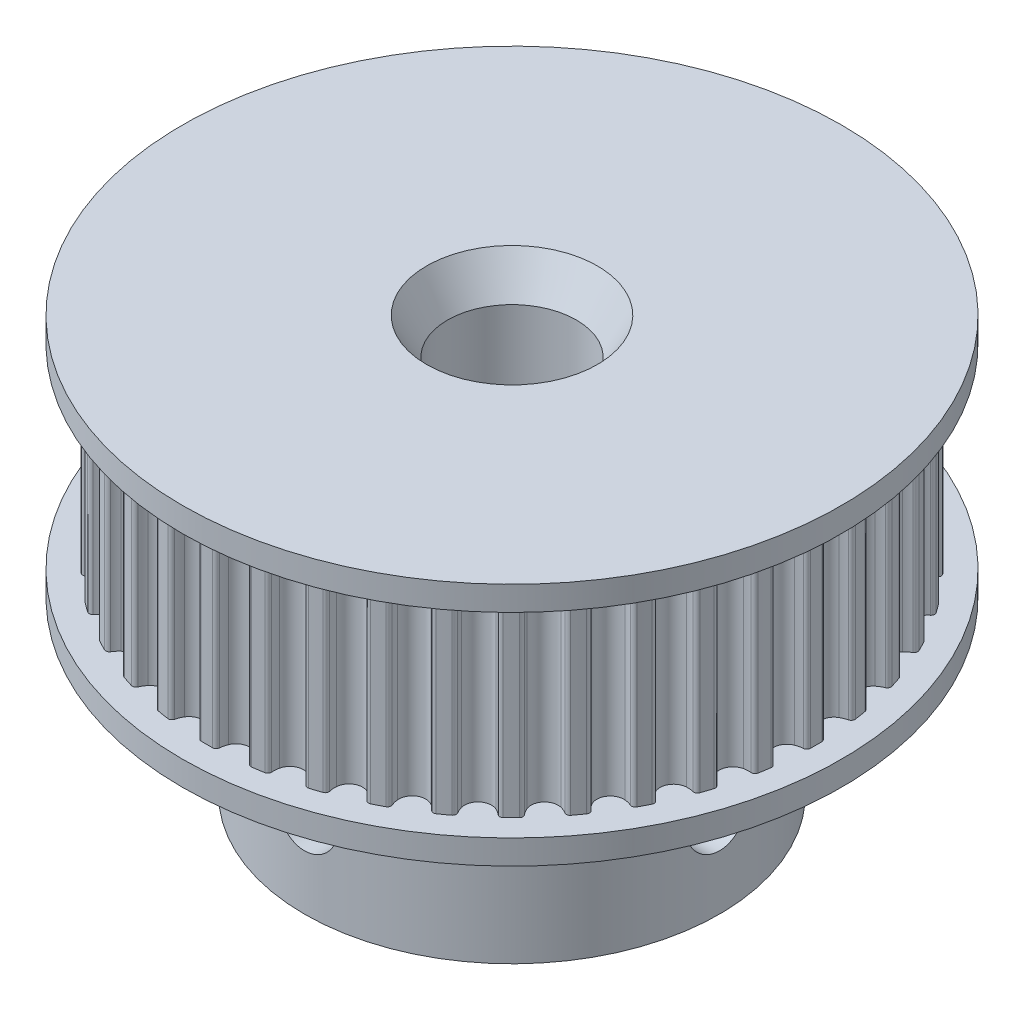
SolidWorks part; units mm, degrees
ref_plane "Front Plane" through (0, 0, 0) normal (0, 0, 1) x (1, 0, 0)
ref_plane "Top Plane" through (0, 0, 0) normal (0, 1, 0) x (1, 0, 0)
ref_plane "Right Plane" through (0, 0, 0) normal (1, 0, 0) x (0, 0, -1)
sketch "Sketch1" plane through (0, 0, 0) normal (0, 1, 0) x (1, 0, 0)
  circle A0 centre (0, 0) radius 13.5
  dimension "D1" = 27
extrude "Boss-Extrude1" add sketch "Sketch1" along normal blind 10
sketch "Sketch6" plane through (0, 0, 0) normal (0, 1, 0) x (1, 0, 0)
  circle A0 centre (0, 0) radius 8.5
  dimension "D2" = 17
extrude "Boss-Extrude2" add sketch "Sketch6" against normal blind 7
sketch "Sketch4" plane through (0, 0, 0) normal (0, 1, 0) x (1, 0, 0)
  circle A1 centre (0, 0) radius 2.64
  dimension "D1" = 5.28
extrude "Cut-Extrude3" cut sketch "Sketch4" along normal through all and the other way through all
ref_plane "Plane1" through (0, 1, 0) normal (0, 1, 0) x (1, 0, 0)
sketch "Sketch2" plane through (0, 1, 0) normal (0, 1, 0) x (1, 0, 0)
  line L0 (0, 0) -> (0, 15.3126) construction
  line L1 (-0.0014, -0.018) -> (0.9816, 12.2246) construction
  line L2 (0, 0) -> (1.407, 12.4893) construction
  line L3 (0, 0) -> (1.1174, 13.9156) construction
  line L4 (0, 12.48) -> (0, 13.8263)
  line L6 (1.9915, 12.3201) -> (2.2063, 13.6491)
  circle A0 centre (0, 0) radius 12.48 construction
  arc A1 (0, 12.48) -> (0.2536, 12.4774) centre (0, 0) cw
  arc A2 (0.2536, 12.4774) -> (0.4002, 12.3379) centre (0.2506, 12.3275) cw
  arc A3 (0.4002, 12.3379) -> (0.4664, 12.0434) centre (1.3978, 12.4077) ccw
  arc A4 (0.4664, 12.0434) -> (1.4613, 11.9635) centre (0.9833, 12.2456) ccw
  circle A5 centre (0, 0) radius 11.73 construction
  circle A6 centre (0, 0) radius 13.11 construction
  arc A7 (1.5737, 12.2437) -> (1.4613, 11.9635) centre (0.6001, 12.4717) cw
  arc A8 (1.7407, 12.358) -> (1.5737, 12.2437) centre (1.7198, 12.2095) ccw
  arc A9 (1.9915, 12.3201) -> (1.7407, 12.358) centre (0, 0) ccw
  arc A10 (0, 13.8263) -> (2.2063, 13.6491) centre (0, 0) cw
  point P16 (0.9989, 12.44)
  point P17 (1.3971, 12.4016)
  point P18 (0.9989, 12.44)
  dimension "D1" = 24.96
  dimension "D2" = 0.15
  dimension "D3" = 1
  dimension "D4" = 0.555
  dimension "D7" = 0.75
  dimension "D8" = 1.38
  dimension "D5" = 0.4
  dimension "D6" = 1
extrude "Cut-Extrude1" cut sketch "Sketch2" along normal blind 8
ref_axis "Axis2" through (0, 10, 0) along (0, -1, 0)
pattern_circular "CirPattern1" count 40 over 360 about axis through (0, 10, 0) along (0, -1, 0) of "Cut-Extrude1"
sketch "Sketch5" plane through (0, 0, 0) normal (0, 0, 1) x (1, 0, 0)
  line L0 (-3.5, 10) -> (0, 10)
  line L1 (13.5, 10) -> (-13.5, 10) construction
  line L5 (-3.5, -7) -> (0, -7)
  line L7 (-3.5, -7) -> (-0.6285, -4.1285)
  line L8 (0, 10) -> (0, 6.1244)
  line L9 (-8.5, -7) -> (8.5, -7) construction
  line L10 (-0.6285, -4.1285) -> (0, -4.1285)
  line L11 (-1.2624, 6.1244) -> (0, 6.1244)
  line L12 (-1.2624, 6.1244) -> (-3.5, 10)
  line L13 (0, -4.1285) -> (0, -7)
  dimension "D1" = 3.5
  dimension "D3" = 3.5
  dimension "D4" = 45
revolve "Cut-Revolve1" cut sketch "Sketch5" angle 360 about axis through (0, 10, 0) along (0, -1, 0)
sketch "Sketch7" plane through (0, 0, 0) normal (0, 0, 1) x (1, 0, 0)
  line L0 (-13.5805, -3.5) -> (12.2971, -3.5) construction
  line L1 (-8.5, 0) -> (8.5, 0) construction
  line L2 (-8.5, -7) -> (8.5, -7) construction
  line L3 (0, 0) -> (0, -10.6921) construction
  circle A0 centre (0, -3.5) radius 1.25
  dimension "D1" = 2.5
extrude "Cut-Extrude4" cut sketch "Sketch7" against normal through all and the other way blind 10
sketch "Sketch8" plane through (0, 0, 0) normal (1, 0, 0) x (0, 0, -1)
  line L0 (-10.2203, -3.5) -> (10.2203, -3.5) construction
  line L1 (-8.5, 0) -> (8.5, 0) construction
  line L2 (-8.5, -7) -> (8.5, -7) construction
  line L3 (0, 0) -> (0, -10.0387) construction
  line L4 (0, 10) -> (0, 0) construction
  circle A0 centre (0, -3.5) radius 1.25
  dimension "D1" = 2.5
extrude "Cut-Extrude5" cut sketch "Sketch8" against normal through all and the other way blind 10
